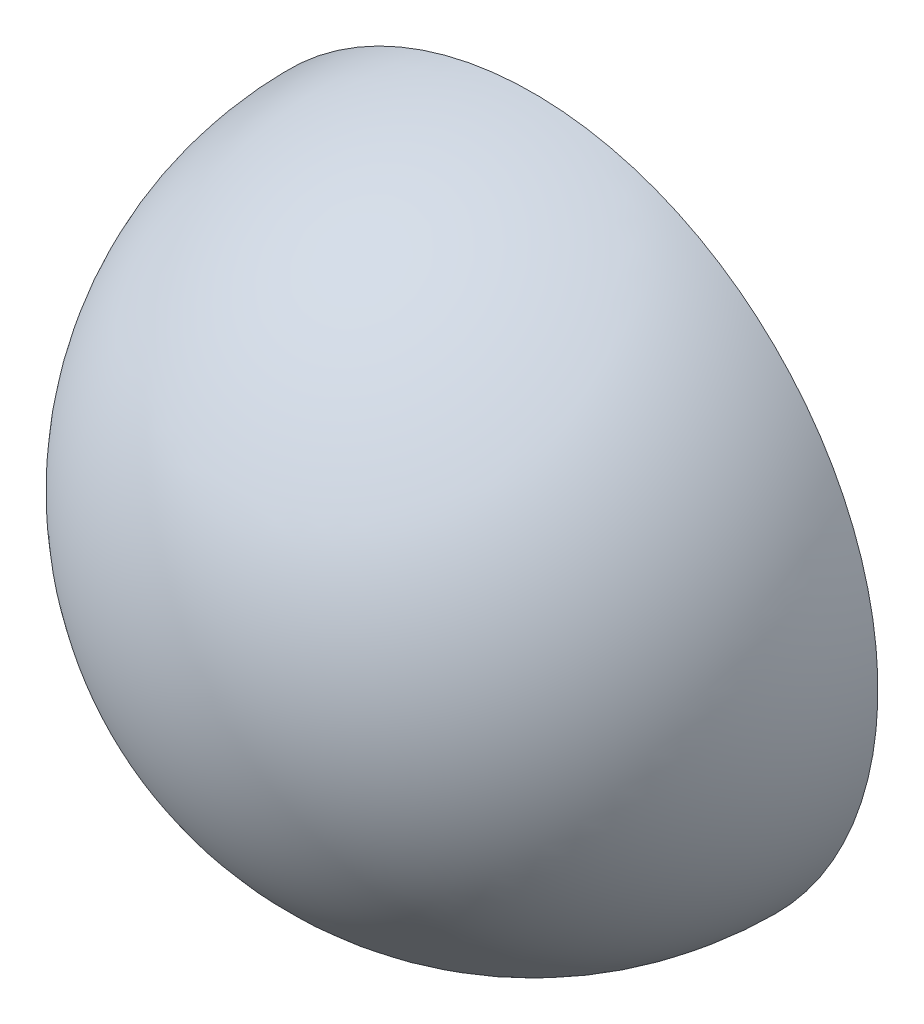
SolidWorks part; units mm, degrees
material "Настроенная пользователем пластмасса"
ref_plane "Спереди" through (0, 0, 0) normal (0, 0, 1) x (1, 0, 0)
ref_plane "Сверху" through (0, 0, 0) normal (0, 1, 0) x (1, 0, 0)
ref_plane "Справа" through (0, 0, 0) normal (1, 0, 0) x (0, 0, -1)
sketch "Эскиз1" plane through (0, 0, 0) normal (0, 1, 0) x (1, 0, 0)
  line L0 (0, 0) -> (0, -3)
  line L1 (0, 0) -> (-3, 0)
  line L2 (0, 0) -> (0, -5.1258) construction
  arc A0 (0, -3) -> (-3, 0) centre (0, 0) cw
  point P5 (0, -5.1258)
  point P6 (0, -2.6164)
  point P7 (0, 0.2891)
  point P8 (0, 0)
  dimension "D1" = 6
revolve "Повернуть1" add sketch "Эскиз1" angle 360 about L2
